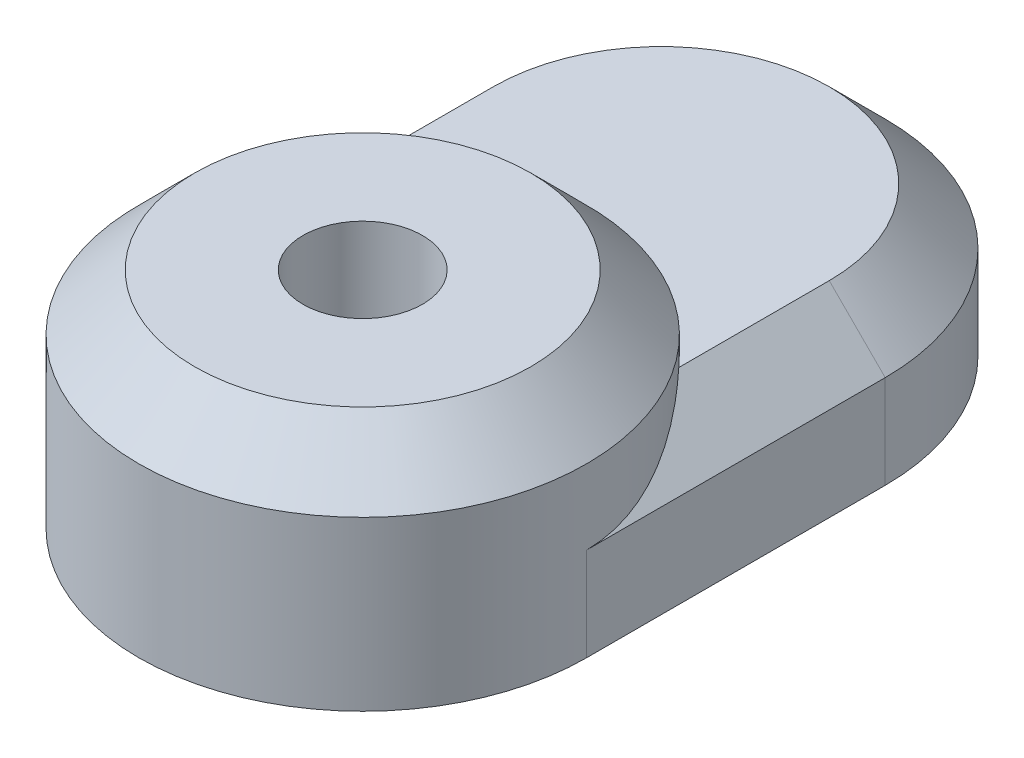
SolidWorks part; units mm, degrees
ref_plane "Front Plane" through (0, 0, 0) normal (0, 0, 1) x (1, 0, 0)
ref_plane "Top Plane" through (0, 0, 0) normal (0, 1, 0) x (1, 0, 0)
ref_plane "Right Plane" through (0, 0, 0) normal (1, 0, 0) x (0, 0, -1)
sketch "Sketch1" plane through (0, 0, 0) normal (0, 1, 0) x (1, 0, 0)
  line L0 (0, 0) -> (0, 8) construction
  line L1 (0, -54.6431) -> (0, 54.6431) construction
  line L2 (-6, 0) -> (-6, 8)
  line L3 (6, 0) -> (6, 8)
  arc A0 (-6, 0) -> (6, 0) centre (0, 0) ccw
  arc A1 (6, 8) -> (-6, 8) centre (0, 8) ccw
  circle A2 centre (0, 0) radius 1.6
  point P5 (0, 4)
  dimension "D3" = 3.2
  dimension "D1" = 12
  dimension "D2" = 8
extrude "Boss-Extrude1" add sketch "Sketch1" along normal blind 4
sketch "Sketch2" plane through (0, 4, 0) normal (0, 1, 0) x (1, 0, 0)
  circle A0 centre (0, 0) radius 1.6 construction
  circle A1 centre (0, 0) radius 1.6
  arc A2 (-6, 0) -> (6, 0) centre (0, 0) ccw construction
  circle A3 centre (0, 0) radius 6
extrude "Boss-Extrude2" add sketch "Sketch2" along normal blind 2
chamfer "Chamfer1" distance 1.5 angle 45 4 edges at (0, 6, 6) (0, 4, -14)
